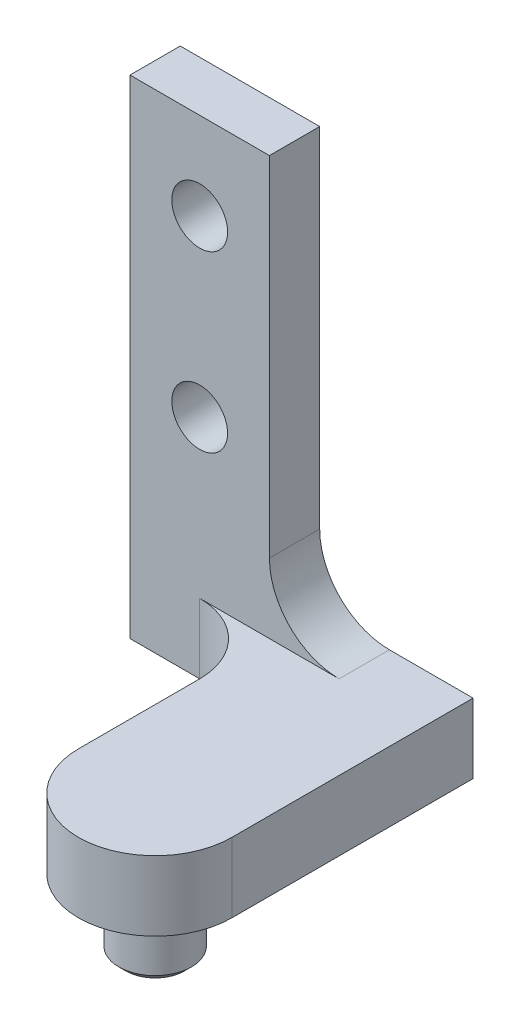
SolidWorks part; units mm, degrees
ref_plane "Front Plane" through (0, 0, 0) normal (0, 0, 1) x (1, 0, 0)
ref_plane "Top Plane" through (0, 0, 0) normal (0, 1, 0) x (1, 0, 0)
ref_plane "Right Plane" through (0, 0, 0) normal (1, 0, 0) x (0, 0, -1)
sketch "Sketch1" plane through (0, 0, 0) normal (0, 1, 0) x (1, 0, 0)
  line L9 (-10.5963, -4.6111) -> (-21.5963, -4.6111)
  line L10 (-10.5963, -4.6111) -> (-10.5963, 12.6889)
  line L11 (-10.5963, 12.6889) -> (-21.5963, 12.6889)
  line L12 (-21.5963, -4.6111) -> (-21.5963, 12.6889)
  circle A0 centre (-16.0963, -4.6111) radius 2.6
  arc A1 (-21.5963, -4.6111) -> (-10.5963, -4.6111) centre (-16.0963, -4.6111) ccw
extrude "Boss-Extrude1" add sketch "Sketch1" along normal blind 5 contours A0 L9 L10 L11 L12 | L9 A1 A0 | L9 A0 | L9 A0 region at (-16.0963, 0, 7.2996) region at (-16.0963, 0, -4.4849) region at (-16.0963, 0, 5.7146) region at (-16.0963, 0, 3.5076)
extrude "Boss-Extrude2" add sketch "Sketch1<3>" against normal blind 5 contours L9 A0 | L9 A0 region at (-16.0963, 0, 5.7146) region at (-16.0963, 0, 3.5076)
sketch "Sketch1<3>" plane through (0, 0, 0) normal (0, 1, 0) x (1, 0, 0) same geometry as "Sketch1"
chamfer "Chamfer1" distance 0.5 angle 45 1 edges at (-16.0963, -5, 7.2111)
fillet "Fillet2" radius 1 1 edges at (-16.0963, 0, 7.2111)
sketch "Sketch4" plane through (0, 0, 0) normal (0, -1, 0) x (1, 0, 0)
  line L1 (-21.5963, -12.6889) -> (-31.5963, -12.6889)
  line L3 (-21.5963, -9.0821) -> (-31.5963, -9.0821)
  line L4 (-31.5963, -12.6889) -> (-31.5963, -9.0821)
  line L5 (-31.5963, -9.0821) -> (-10.5963, -9.0821)
  line L6 (-31.5963, -9.0821) -> (-31.5963, -12.6889)
  line L7 (-31.5963, -12.6889) -> (-10.5963, -12.6889)
  line L8 (-10.5963, -9.0821) -> (-10.5963, -12.6889)
  line M4 (-21.5963, 4.6111) -> (-21.5963, -12.6889)
extrude "Boss-Extrude4" add sketch "Sketch4" against normal blind 35 contours L4 L1 L3 M4 region at (-26.5963, 0, -10.8855)
fillet "Fillet4" radius 5 1 edges at (-21.5963, 2.5, -9.0821)
fillet "Fillet5" radius 5 1 edges at (-21.5963, 5, -10.8855)
sketch "Sketch5" plane through (0, 0, -9.0821) normal (0, 0, 1) x (1, 0, 0)
  circle A0 centre (-26.5963, 28.75) radius 2
  circle A1 centre (-26.5963, 16.25) radius 2
extrude "Cut-Extrude2" cut sketch "Sketch5" against normal blind 35
